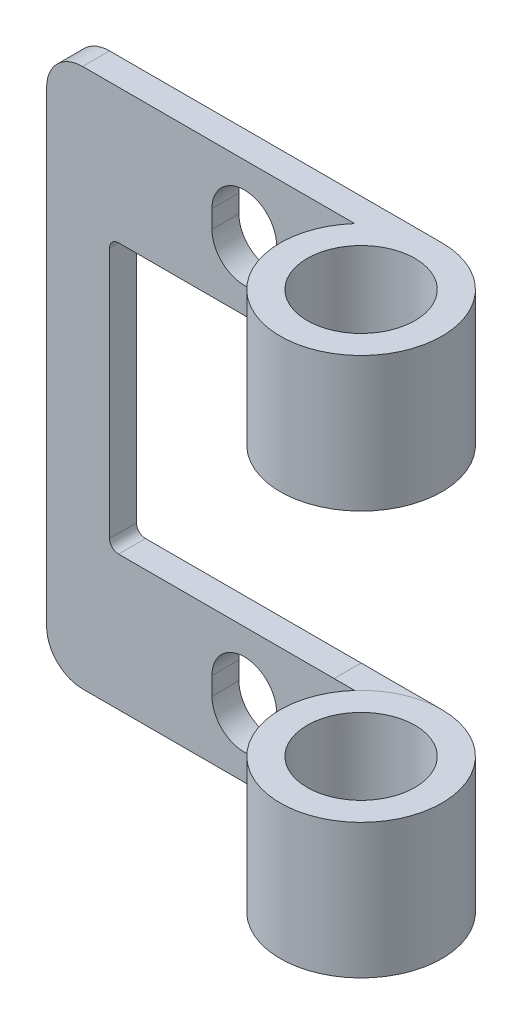
SolidWorks part; units mm, degrees
ref_plane "Спереди" through (0, 0, 0) normal (0, 0, 1) x (1, 0, 0)
ref_plane "Сверху" through (0, 0, 0) normal (0, 1, 0) x (1, 0, 0)
ref_plane "Справа" through (0, 0, 0) normal (1, 0, 0) x (0, 0, -1)
sketch "Эскиз2" plane through (0, 0, 0) normal (0, 0, 1) x (1, 0, 0)
  line L1 (0, 0) -> (16, 0)
  line L2 (0, 0) -> (0, -30)
  line L3 (0, -30) -> (16, -30)
  line L4 (16, 0) -> (16, -30)
  dimension "D1" = 30
  dimension "D2" = 16
base flange "Базовая кромка1" sketch "Эскиз2" thickness 1.5 reverse thickness direction no parameters "D1"=1.7
sketch "Эскиз7" plane through (0, -30, 0) normal (0, -1, 0) x (1, 0, 0)
  line L0 (8, -1.5) -> (30.4955, -1.5) construction
  line L1 (0, -1.5) -> (16, -1.5) construction
  line L2 (16, -1.5) -> (16, 8.0998) construction
  circle A0 centre (20.5, 3) radius 3
  dimension "D1" = 6
  dimension "D2" = 4.5
  dimension "D3" = 4.5
extrude "Вытянуть-Тонкостенный1" add sketch "Эскиз7" against normal blind 30 thin thin type one direction wall 1.5
sketch "Эскиз8" plane through (16, 0, 0) normal (1, 0, 0) x (0, 0, -1)
  line L0 (0, -30) -> (0, 0) construction
  line L1 (1.5, -30) -> (0, -30)
  line L2 (1.5, -30) -> (1.5, -22.5)
  line L3 (1.5, -22.5) -> (0, -22.5)
  line L4 (0, -30) -> (0, -22.5)
  line L5 (1.5, -15) -> (0, -15) construction
  line L6 (1.5, -30) -> (1.5, 0) construction
  line L7 (1.5, 0) -> (0, 0)
  line L8 (0, 0) -> (0, -7.5)
  line L9 (1.5, 0) -> (1.5, -7.5)
  line L10 (1.5, -7.5) -> (0, -7.5)
  dimension "D1" = 7.5
extrude "Бобышка-Вытянуть1" add sketch "Эскиз8" along normal blind 4.5
sketch "Эскиз9" plane through (0, 0, -1.5) normal (0, 0, 1) x (1, 0, 0)
  line L0 (0, -30) -> (17.1459, -30) construction
  line L1 (3.5, -22.5) -> (28.5, -22.5)
  line L2 (3.5, -22.5) -> (3.5, -7.5)
  line L3 (3.5, -7.5) -> (28.5, -7.5)
  line L4 (28.5, -22.5) -> (28.5, -7.5)
  line L5 (17.1459, 0) -> (0, 0) construction
  line L6 (0, 0) -> (0, -30) construction
  dimension "D1" = 7.5
  dimension "D2" = 7.5
  dimension "D3" = 3.5
  dimension "D4" = 25
extrude "Вырез-Вытянуть1" cut sketch "Эскиз9" along normal through all normal cut yes
fillet "Скругление1" radius 2 2 edges at (0, 0, -0.75) (0, -30, -0.75)
sketch "Эскиз10" plane through (0, 0, 0) normal (0, 0, 1) x (1, 0, 0)
  line L0 (11, -26.75) -> (11, -25.75) construction
  line L1 (9.2, -26.75) -> (9.2, -25.75)
  line L2 (12.8, -26.75) -> (12.8, -25.75)
  line L3 (11, -35.8341) -> (11, -16.3926) construction
  line L5 (2, -30) -> (17.1459, -30) construction
  line L6 (0, -15) -> (3.5, -15) construction
  line L7 (0, -2) -> (0, -28) construction
  line L8 (3.5, -22.5) -> (3.5, -7.5) construction
  line L9 (11, -3.25) -> (11, -4.25) construction
  line L10 (9.2, -3.25) -> (9.2, -4.25)
  line L11 (12.8, -3.25) -> (12.8, -4.25)
  arc A0 (9.2, -26.75) -> (12.8, -26.75) centre (11, -26.75) ccw
  arc A1 (12.8, -25.75) -> (9.2, -25.75) centre (11, -25.75) ccw
  arc A2 (9.2, -3.25) -> (12.8, -3.25) centre (11, -3.25) cw
  arc A3 (12.8, -4.25) -> (9.2, -4.25) centre (11, -4.25) cw
  point P2 (11, -26.25)
  point P20 (11, -3.75)
  dimension "D2" = 1.8
  dimension "D1" = 1
  dimension "D3" = 5
  dimension "D4" = 3.75
extrude "Вырез-Вытянуть2" cut sketch "Эскиз10" against normal blind 10 normal cut yes
fillet "Скругление2" radius 0.5 2 edges at (3.5, -7.5, -0.75) (3.5, -22.5, -0.75)
sketch "Сгиб-Линии1" [suppressed] plane through (0, 0, 0) normal (0, 1, 0) x (1, 0, 0)
sketch "Граничная рамка1" [suppressed] plane through (0, 0, 0) normal (0, 1, 0) x (1, 0, 0)
sheet metal parameters "Листовой металл1" thickness 1.5 parameters "D1"=1.7
flat pattern "Развертка1" [suppressed]
sketch "Сгиб-Линии2" plane through (0, 0, 0) normal (0, 1, 0) x (1, 0, 0)
sketch3d "Граничная рамка2" [suppressed]
  line L0 (-14, 0, 0) -> (-14, -30, 0) construction
  line L1 (0, 0, 0) -> (0, -30, 0) construction
  line L2 (-14, 0, 0) -> (0, 0, 0) construction
  line L3 (-14, -30, 0) -> (0, -30, 0) construction
sheet metal parameters "Листовой металл2" thickness 1.5 parameters "D1"=1.7
flat pattern "Развертка1"
sketch "Сгиб-Линии2" plane through (0, 0, 0) normal (0, 1, 0) x (1, 0, 0)
sketch3d "Граничная рамка2" [suppressed]
  line L0 (13.8377, 0, 0) -> (13.8377, -30, 0) construction
  line L1 (0, 0, 0) -> (0, -30, 0) construction
  line L2 (13.8377, 0, 0) -> (0, 0, 0) construction
  line L3 (13.8377, -30, 0) -> (0, -30, 0) construction
sheet metal parameters "Листовой металл3" thickness 1.5 parameters "D1"=1.7
flat pattern "Развертка1"
sketch "Сгиб-Линии2" plane through (0, 0, 0) normal (0, 1, 0) x (1, 0, 0)
sketch3d "Граничная рамка2" [suppressed]
  line L0 (15.1459, 0, 0) -> (15.1459, -30, 0) construction
  line L1 (0, 0, 0) -> (0, -30, 0) construction
  line L2 (15.1459, 0, 0) -> (0, 0, 0) construction
  line L3 (15.1459, -30, 0) -> (0, -30, 0) construction
sheet metal parameters "Листовой металл4" thickness 1.5 parameters "D1"=1.7
flat pattern "Развертка1"
sketch "Сгиб-Линии2" plane through (0, 0, 0) normal (0, 1, 0) x (1, 0, 0)
sketch3d "Граничная рамка2" [suppressed]
  line L0 (17.1459, -30, 0) -> (17.1459, 0, 0) construction
  line L1 (0, -30, 0) -> (0, 0, 0) construction
  line L2 (17.1459, -30, 0) -> (0, -30, 0) construction
  line L3 (17.1459, 0, 0) -> (0, 0, 0) construction
sheet metal parameters "Листовой металл5" thickness 1.5 parameters "D1"=1.7
flat pattern "Развертка1"
sketch "Сгиб-Линии2" plane through (0, 0, 0) normal (0, 1, 0) x (1, 0, 0)
sketch3d "Граничная рамка2" [suppressed]
  line L0 (17.1459, -30, 0) -> (17.1459, 0, 0) construction
  line L1 (0, -30, 0) -> (0, 0, 0) construction
  line L2 (17.1459, -30, 0) -> (0, -30, 0) construction
  line L3 (17.1459, 0, 0) -> (0, 0, 0) construction
